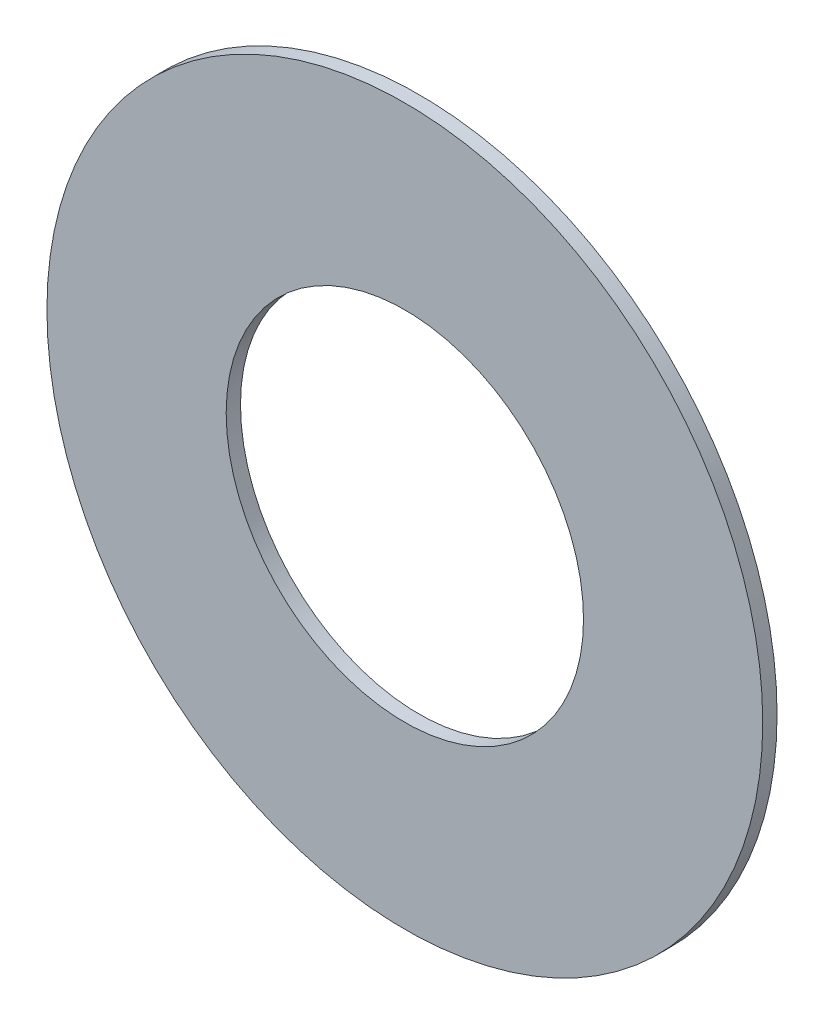
SolidWorks part; units mm, degrees
ref_plane "Front Plane" through (0, 0, 0) normal (0, 0, 1) x (1, 0, 0)
ref_plane "Top Plane" through (0, 0, 0) normal (0, 1, 0) x (1, 0, 0)
ref_plane "Right Plane" through (0, 0, 0) normal (1, 0, 0) x (0, 0, -1)
sketch "Sketch1" plane through (0, 0, 0) normal (0, 0, 1) x (1, 0, 0)
  circle A0 centre (0, 0) radius 39.624
  circle A1 centre (0, 0) radius 79.375
  dimension "D1" = 158.75
  dimension "D2" = 79.248
extrude "Boss-Extrude1" add sketch "Sketch1" along normal blind 3.175
